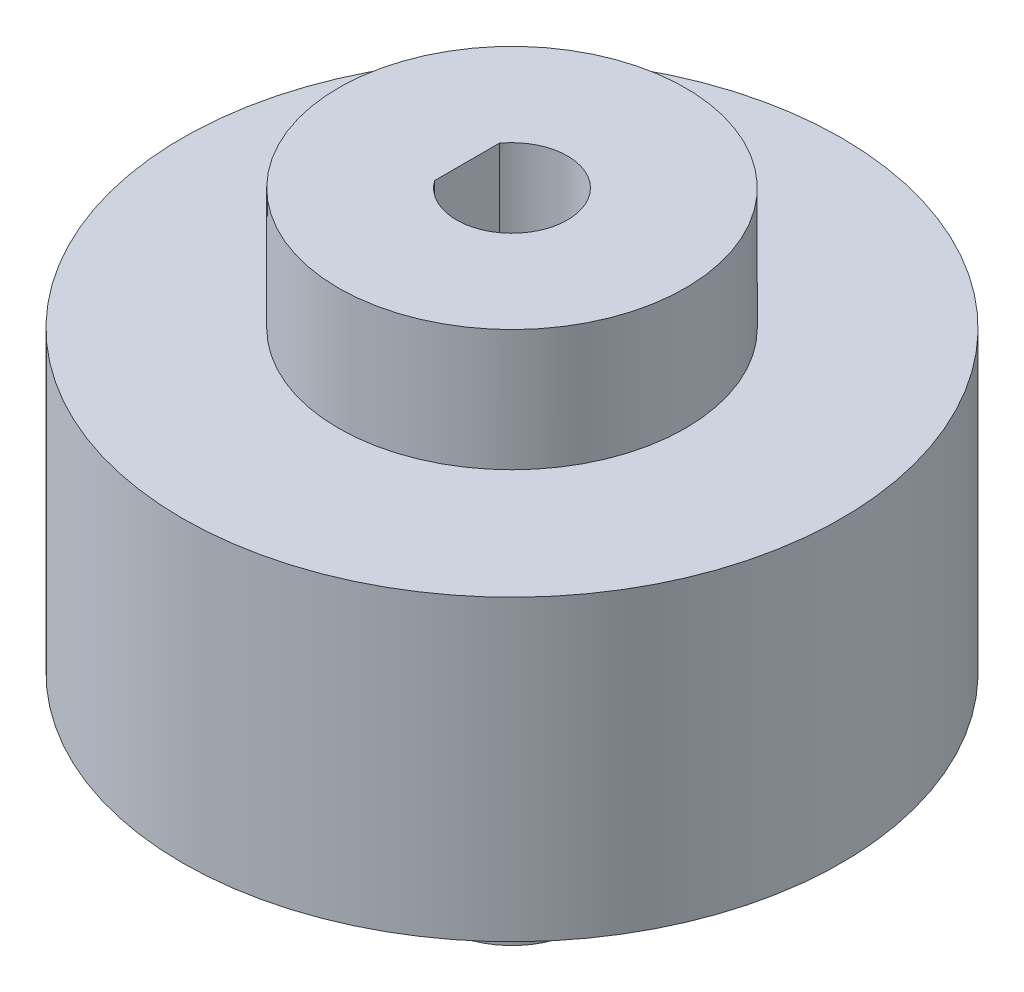
SolidWorks part; units mm, degrees
ref_plane "Plan de face" through (0, 0, 0) normal (0, 0, 1) x (1, 0, 0)
ref_plane "Plan de dessus" through (0, 0, 0) normal (0, 1, 0) x (1, 0, 0)
ref_plane "Plan de droite" through (0, 0, 0) normal (1, 0, 0) x (0, 0, -1)
sketch "Esquisse1" plane through (0, 0, 0) normal (0, 1, 0) x (1, 0, 0)
  circle A0 centre (0, 0) radius 4
  dimension "D1" = 8
extrude "Boss.-Extru.1" add sketch "Esquisse1" against normal blind 35
sketch "Esquisse2" plane through (0, 0, 0) normal (0, 1, 0) x (1, 0, 0)
  circle A0 centre (0, 0) radius 3.2
  dimension "D1" = 6.4
extrude "Enlèv. mat.-Extru.1" cut sketch "Esquisse2" against normal blind 13
sketch "Esquisse4" plane through (0, -13, 0) normal (0, 1, 0) x (1, 0, 0)
  line L0 (0, 0) -> (-2.6, 0)
  line L1 (-2.6, 0) -> (-2.6, -1.8655)
  line L2 (-2.6, -1.8655) -> (-3.3205, -1.8655)
  line L3 (-2.6, 0) -> (-2.6, 1.8655)
  line L5 (-2.6, 1.8655) -> (-3.3205, 1.8655)
  line L6 (-2.6, 1.8655) -> (-2.6, -1.8655)
  line L7 (-2.6, -1.8655) -> (-3.3205, -1.8655)
  line L8 (-3.3205, 1.8655) -> (-3.3205, -1.8655)
  circle A0 centre (0, 0) radius 3.2 construction
  circle M2 centre (0, 0) radius 3.2
  dimension "D1" = 2.6
extrude "Boss.-Extru.2" add sketch "Esquisse4" along normal blind 13 contours L1 L3 M2 region at (-2.842, -13, 0)
sketch "Esquisse5" plane through (0, 0, 0) normal (0, 1, 0) x (1, 0, 0)
  circle A0 centre (0, 0) radius 10
  circle A1 centre (0, 0) radius 4
  dimension "D1" = 20
extrude "Boss.-Extru.3" add sketch "Esquisse5" against normal blind 7
sketch "Sketch2" plane through (0, -7, 0) normal (0, -1, 0) x (1, 0, 0)
  circle A0 centre (0, 0) radius 16.2
  circle A1 centre (0, 0) radius 19
  circle A2 centre (0, 0) radius 4
  dimension "D1" = 32.4
  dimension "D2" = 38
extrude "Boss-Extrude4" add sketch "Sketch2" along normal blind 3 contours A0 | A2
extrude "Boss-Extrude5" add sketch "Sketch2<8>" along normal blind 17.2 contours A1 A0 region at (-18.4626, -7, 0)
sketch "Sketch2<8>" plane through (0, -7, 0) normal (0, -1, 0) x (1, 0, 0) same geometry as "Sketch2"
ref_plane "Plane1" through (0, 0, -19) normal (0, 0, -1) x (-1, 0, 0)
sketch "Sketch4" plane through (0, 0, -19) normal (0, 0, -1) x (-1, 0, 0)
  line L0 (-19, -24.2) -> (19, -24.2) construction
  circle A0 centre (0, -16.6) radius 3
  dimension "D1" = 6
  dimension "D2" = 7.6
extrude "Cut-Extrude1" cut sketch "Sketch4" against normal blind 10
